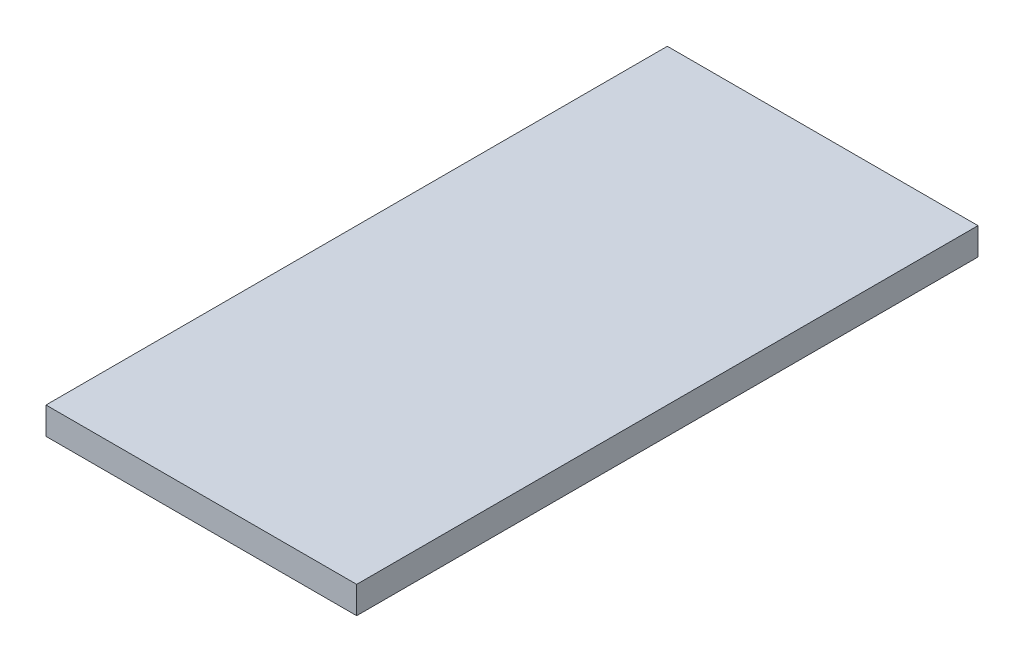
SolidWorks part; units mm, degrees
ref_plane "Front Plane" through (0, 0, 0) normal (0, 0, 1) x (1, 0, 0)
ref_plane "Top Plane" through (0, 0, 0) normal (0, 1, 0) x (1, 0, 0)
ref_plane "Right Plane" through (0, 0, 0) normal (1, 0, 0) x (0, 0, -1)
sketch "Sketch1" plane through (0, 0, 0) normal (0, 1, 0) x (1, 0, 0)
  line L1 (-508, 1016) -> (508, 1016)
  line L2 (-508, 1016) -> (-508, -1016)
  line L3 (-508, -1016) -> (508, -1016)
  line L4 (508, 1016) -> (508, -1016)
  line L5 (-508, 1016) -> (508, -1016) construction
  line L6 (-508, -1016) -> (508, 1016) construction
  point P0 (0, 0)
  dimension "D1" = 1016
  dimension "D2" = 2032
extrude "Boss-Extrude1" add sketch "Sketch1" along normal blind 88.9
